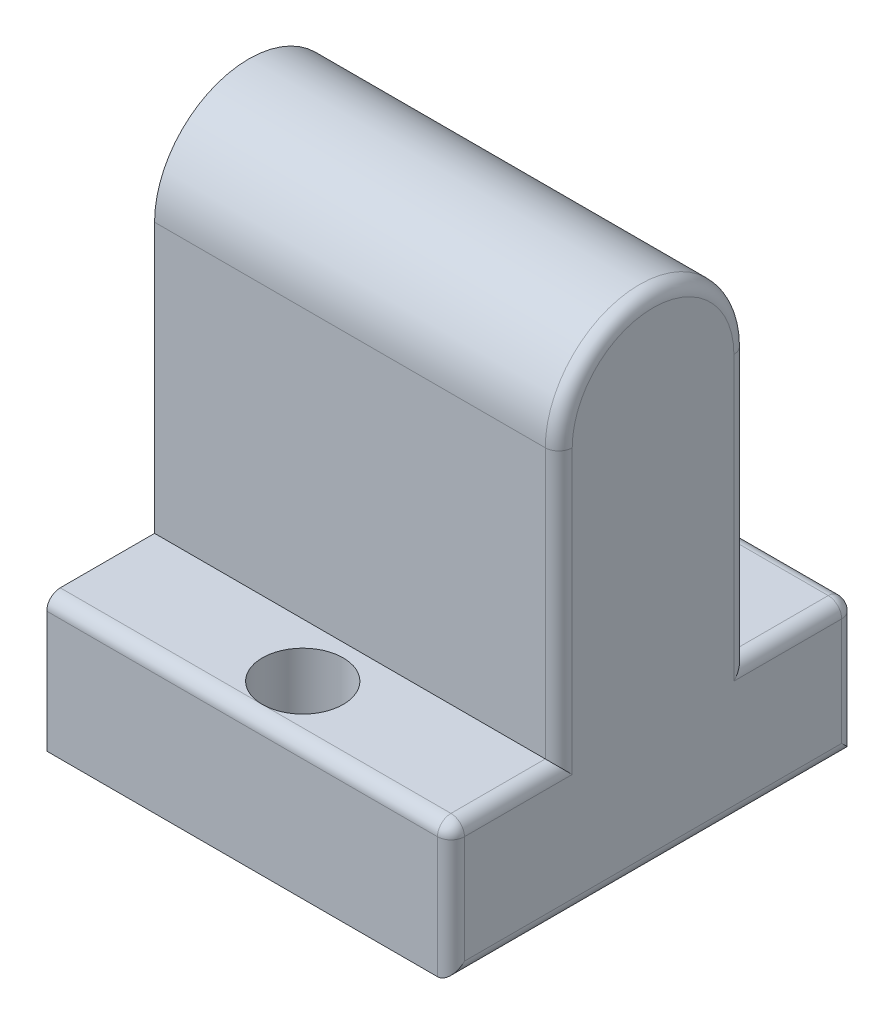
SolidWorks part; units mm, degrees
ref_plane "Front Plane" through (0, 0, 0) normal (0, 0, 1) x (1, 0, 0)
ref_plane "Top Plane" through (0, 0, 0) normal (0, 1, 0) x (1, 0, 0)
ref_plane "Right Plane" through (0, 0, 0) normal (1, 0, 0) x (0, 0, -1)
sketch "Sketch1" plane through (0, 0, 0) normal (1, 0, 0) x (0, 0, -1)
  line L0 (-7, 0) -> (-7, -20)
  line L1 (7, 0) -> (7, -20)
  line L2 (7, -20) -> (-7, -20)
  circle A0 centre (0, 0) radius 4
  arc A1 (7, 0) -> (-7, 0) centre (0, 0) ccw
  dimension "D1" = 8
  dimension "D2" = 3
  dimension "D3" = 20
extrude "Boss-Extrude3" add sketch "Sketch1" along normal blind 30
sketch "Sketch3" plane through (0, -20, 0) normal (0, -1, 0) x (1, 0, 0)
  line L0 (0, 7) -> (30, -7) construction
  line L1 (0, -7) -> (30, 7) construction
  line L3 (0, -15) -> (30, -15)
  line L4 (0, -15) -> (0, 15)
  line L5 (0, 15) -> (30, 15)
  line L6 (30, -15) -> (30, 15)
  line L7 (0, -15) -> (30, 15) construction
  line L8 (0, 15) -> (30, -15) construction
  point P8 (15, 0)
  dimension "D1" = 30
  dimension "D2" = 30
extrude "Boss-Extrude4" add sketch "Sketch3" along normal blind 10
sketch "Sketch4" plane through (0, -20, 0) normal (0, 1, 0) x (1, 0, 0)
  circle A0 centre (15, 11) radius 3
  circle A1 centre (15, -11) radius 3
  dimension "D1" = 6
extrude "Cut-Extrude1" cut sketch "Sketch4" against normal blind 10
sketch "Sketch5" plane through (30, 0, 0) normal (1, 0, 0) x (0, 0, -1)
  circle A0 centre (0, 0) radius 4 construction
  circle A1 centre (0, 0) radius 4
extrude "Boss-Extrude5" add sketch "Sketch5" against normal blind 5
fillet "Fillet2" radius 1 10 edges at (30, -10, -7) (30, -20, -11) (30, -25, -15) (30, -30, 0) (30, -25, 15) (30, -20, 11) (30, -10, 7) (30, 7, 0) (15, -20, -15) (15, -20, 15)
